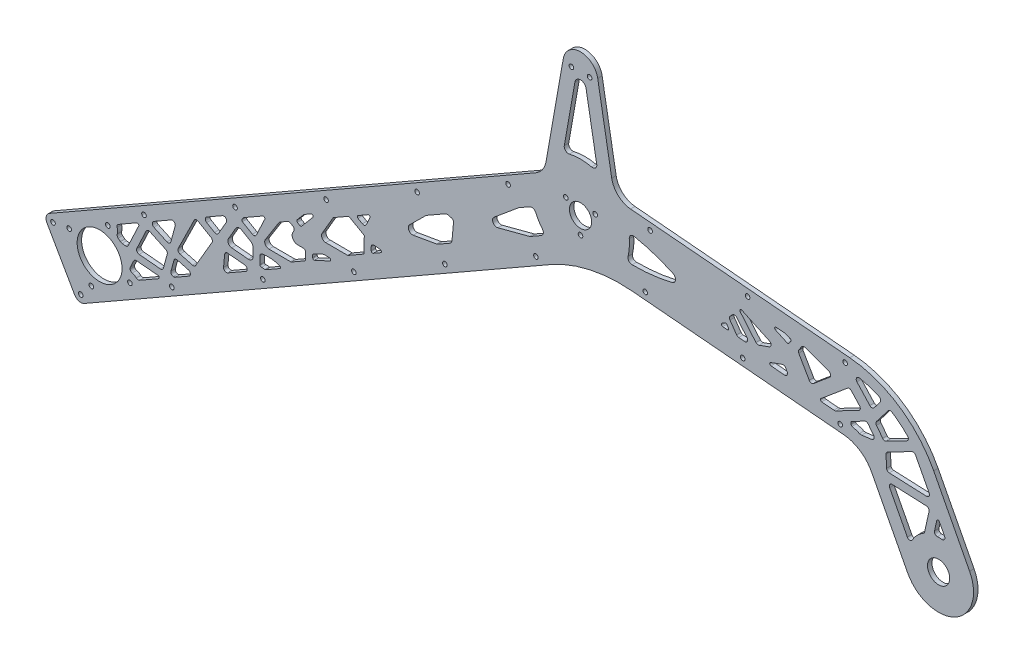
SolidWorks part; units mm, degrees
material "6061-T6 (SS)"
ref_plane "Front Plane" through (0, 0, 0) normal (0, 0, 1) x (1, 0, 0)
ref_plane "Top Plane" through (0, 0, 0) normal (0, 1, 0) x (1, 0, 0)
ref_plane "Right Plane" through (0, 0, 0) normal (1, 0, 0) x (0, 0, -1)
sketch "Reference Sketch" plane through (0, 0, 0) normal (0, 0, 1) x (1, 0, 0)
  line L0 (-343.92, -196.825) -> (0, 0) construction
  line L1 (-243.92, 103.175) -> (356.08, 103.175) construction
  line L2 (-243.92, 103.175) -> (-243.92, 0) construction
  line L3 (-243.92, 0) -> (356.08, 0) construction
  line L4 (356.08, 103.175) -> (356.08, 0) construction
  line L5 (0, 0) -> (256.08, -92.7116) construction
  line L6 (256.08, -92.7116) -> (56.08, -196.825) construction
  line L7 (256.08, -92.7116) -> (456.08, -196.825) construction
  line L8 (-343.92, -196.825) -> (56.08, -196.825) construction
  line L9 (56.08, -196.825) -> (456.08, -196.825) construction
  circle A1 centre (-343.92, -196.825) radius 100 construction
  circle A2 centre (56.08, -196.825) radius 100 construction
  circle A3 centre (456.08, -196.825) radius 100 construction
  circle A4 centre (-343.92, -196.825) radius 16.05 construction
  circle A5 centre (-343.92, -196.825) radius 28.55 construction
  circle A6 centre (-343.92, -196.825) radius 38.55 construction
  circle A7 centre (-343.92, -196.825) radius 33.55 construction
  point P13 (-343.92, -296.825)
  point P14 (556.08, -196.825)
  point P17 (-443.92, -196.825)
  dimension "D3" = 32.1
  dimension "D5" = 200
  dimension "D9" = 57.1
  dimension "D10" = 10
  dimension "D11" = 5
  dimension "D1" = 600
  dimension "D2" = 103.175
  dimension "D4" = 243.92
  dimension "D6" = 125
  dimension "D7" = 400
  dimension "D8" = 1000
sketch "Sketch2" plane through (0, 0, 0) normal (0, 0, 1) x (1, 0, 0)
  line L0 (-379.7168, -188.5069) -> (-32.0065, 10.4873)
  line L1 (-354.8814, -231.9028) -> (-21.5627, -41.1449)
  line L2 (-343.92, -196.825) -> (0, 0) construction
  line L3 (-184.3777, -76.7146) -> (-159.5423, -120.1104) construction
  line L4 (-24.685, 20.9013) -> (-12.3101, 91.0831)
  line L5 (12.3101, 91.0831) -> (22.322, 34.3028)
  line L6 (0, 98.4125) -> (0, 112.7) construction
  line L7 (-5.4848, 79.4125) -> (5.4848, 79.4125) construction
  line L8 (5.4848, 79.4125) -> (10.9697, 88.9125) construction
  line L9 (10.9697, 88.9125) -> (5.4848, 98.4125) construction
  line L10 (5.4848, 98.4125) -> (-5.4848, 98.4125) construction
  line L11 (-5.4848, 98.4125) -> (-10.9697, 88.9125) construction
  line L12 (-10.9697, 88.9125) -> (-5.4848, 79.4125) construction
  line L13 (-243.92, 103.175) -> (356.08, 103.175) construction
  line L14 (0, 88.9125) -> (0, 0) construction
  line L15 (35.7868, 21.9646) -> (192.5861, 8.2464)
  line L16 (252.5753, -31.8371) -> (278.2553, -81.1679)
  line L17 (233.9047, -104.2553) -> (208.2247, -54.9245)
  line L18 (36.8237, -28.3172) -> (188.2284, -41.5633)
  line L19 (0, 0) -> (192.5861, -16.8491) construction
  line L21 (-365.6311, -190.9191) -> (-338.0141, -175.1139) construction
  line L22 (-381.5729, -195.33) -> (-361.7045, -230.0467)
  line L23 (256.08, -92.7116) -> (56.08, -196.825) construction
  line L25 (-243.92, 0) -> (356.08, 0) construction
  circle A0 centre (0, 0) radius 7.9375
  circle A1 centre (-343.92, -196.825) radius 16.05
  arc A3 (-12.3101, 91.0831) -> (12.3101, 91.0831) centre (0, 88.9125) cw
  circle A4 centre (0, 88.9125) radius 6.5 construction
  circle A5 centre (-6.5, 88.9125) radius 1.65
  circle A6 centre (6.5, 88.9125) radius 1.65
  circle A7 centre (0, 88.9125) radius 9.5 construction
  arc A8 (252.5753, -31.8371) -> (192.5861, 8.2464) centre (186.0495, -66.4682) ccw
  circle A9 centre (256.08, -92.7116) radius 7.9375
  arc A10 (278.2553, -81.1679) -> (233.9047, -104.2553) centre (256.08, -92.7116) cw
  arc A11 (-21.5627, -41.1449) -> (36.8237, -28.3172) centre (28.1082, -127.9366) cw
  arc A12 (188.2284, -41.5633) -> (208.2247, -54.9245) centre (186.0495, -66.4682) cw
  arc A13 (22.322, 34.3028) -> (35.7868, 21.9646) centre (37.0941, 36.9075) ccw
  arc A14 (-32.0065, 10.4873) -> (-24.685, 20.9013) centre (-39.4572, 23.506) ccw
  circle A17 centre (-343.92, -196.825) radius 22.5 construction
  circle A18 centre (-365.6311, -190.9191) radius 1.65
  circle A19 centre (-338.0141, -175.1139) radius 1.65
  circle A20 centre (-322.2089, -202.7309) radius 1.65
  circle A21 centre (-349.8259, -218.5361) radius 1.65
  arc A27 (-379.7168, -188.5069) -> (-381.5729, -195.33) centre (-377.2333, -192.8465) ccw
  arc A28 (-361.7045, -230.0467) -> (-354.8814, -231.9028) centre (-357.3649, -227.5632) ccw
  circle A29 centre (-343.92, -196.825) radius 33.55 construction
  circle A32 centre (-343.92, -196.825) radius 38.55 construction
  point P16 (-171.96, -98.4125)
  point P64 (-343.92, -196.825)
  dimension "D1" = 15.875
  dimension "D2" = 32.1
  dimension "D3" = 45
  dimension "D5" = 13
  dimension "D6" = 3.3
  dimension "D7" = 6
  dimension "D12" = 50
  dimension "D14" = 100
  dimension "D16" = 15
  dimension "D17" = 5
  dimension "D18" = 25
  dimension "D19" = 3.3
  dimension "D15" = 4
  dimension "D4" = 50
  dimension "D8" = 19
  dimension "D9" = 14.2875
  dimension "D10" = 9.525
  dimension "D11" = 10
  dimension "D13" = 50
extrude "Base" add sketch "Sketch2" along normal blind 3.175
sketch "Sketch3" plane through (0, 0, 3.175) normal (0, 0, 1) x (1, 0, 0)
  line L0 (-343.92, -196.825) -> (0, 0) construction
  line L5 (0, 0) -> (197.3986, -17.2701) construction
  line L6 (192.5861, 8.2464) -> (35.7868, 21.9646) construction
  line L9 (36.8237, -28.3172) -> (188.2284, -41.5633) construction
  line L10 (-31.8958, -41.2976) -> (0, 0) construction
  line L11 (0, 0) -> (46.2693, -24.1244) construction
  circle A0 centre (-357.3649, -227.5632) radius 1.65
  circle A1 centre (-343.92, -196.825) radius 33.55 construction
  arc A2 (-361.7045, -230.0467) -> (-354.8814, -231.9028) centre (-357.3649, -227.5632) ccw construction
  circle A3 centre (-292.2711, -190.3101) radius 1.65
  circle A4 centre (-227.1773, -153.057) radius 1.65
  circle A5 centre (-162.0835, -115.8038) radius 1.65
  circle A6 centre (-96.9897, -78.5507) radius 1.65
  circle A7 centre (-31.8958, -41.2976) radius 1.65
  circle A8 centre (-312.1394, -155.5934) radius 1.65
  circle A9 centre (-377.2333, -192.8465) radius 1.65
  circle A10 centre (-247.0456, -118.3403) radius 1.65
  circle A11 centre (-181.9518, -81.0871) radius 1.65
  circle A12 centre (-116.858, -43.834) radius 1.65
  circle A13 centre (-51.7642, -6.5809) radius 1.65
  circle A14 centre (46.2693, -24.1244) radius 1.65
  circle A15 centre (116.0029, -30.2253) radius 1.65
  circle A16 centre (185.7366, -36.3262) radius 1.65
  circle A17 centre (189.2228, 3.5215) radius 1.65
  circle A18 centre (119.4892, 9.6224) radius 1.65
  circle A19 centre (49.7555, 15.7234) radius 1.65
  dimension "D1" = 3.3
  dimension "D2" = 6
  dimension "D3" = 5
  dimension "D5" = 3
  dimension "D4" = 75
  dimension "D6" = 70
extrude "Strut Holes" cut sketch "Sketch3" against normal through all
sketch "Sketch6" plane through (0, 0, 3.175) normal (0, 0, 1) x (1, 0, 0)
  line L0 (-315.2692, -197.7109) -> (-301.7593, -189.9792)
  line L1 (-354.8814, -231.9028) -> (-21.5627, -41.1449) construction
  line L2 (-289.845, -183.1607) -> (-279.9388, -177.4914)
  line L3 (-225.0683, -146.089) -> (-215.0659, -140.3647)
  line L4 (-202.4189, -105.5114) -> (-200.6862, -106.5205)
  line L5 (-330.4255, -170.6672) -> (-317.3783, -163.2003)
  line L6 (-32.0065, 10.4873) -> (-379.7168, -188.5069) construction
  line L7 (-315.9769, -164.4942) -> (-323.4022, -180.2613)
  line L8 (-325.3934, -181.4009) -> (-327.8261, -181.1787)
  line L9 (-302.165, -188.1154) -> (-317.5291, -186.7124)
  line L10 (-319.5204, -187.852) -> (-321.9207, -192.9489)
  line L11 (-295.5333, -171.6316) -> (-298.2962, -181.7883)
  line L12 (-300.4079, -183.2551) -> (-315.6625, -181.8621)
  line L13 (-317.2901, -179.0183) -> (-310.6415, -164.9005)
  line L14 (-307.9799, -163.9432) -> (-296.6111, -169.2972)
  line L15 (-280.4073, -173.8257) -> (-288.2923, -171.6808)
  line L16 (-290.7472, -173.0857) -> (-292.8686, -180.8843)
  line L17 (-292.7787, -149.122) -> (-305.2156, -156.2396)
  line L18 (-305.0743, -159.7848) -> (-295.766, -164.1685)
  line L19 (-292.984, -162.8841) -> (-289.8554, -151.3828)
  line L20 (-286.4122, -167.0105) -> (-277.4777, -169.4409)
  line L21 (-275.2245, -168.5176) -> (-263.487, -148.3649)
  line L22 (-264.2087, -145.6301) -> (-273.4911, -140.2238)
  line L23 (-276.2919, -141.0684) -> (-287.6814, -164.1971)
  line L24 (-267.3269, -134.556) -> (-255.9817, -128.0631)
  line L25 (-253.26, -130.8055) -> (-258.9575, -140.5878)
  line L26 (-261.6923, -141.3094) -> (-267.3401, -138.02)
  line L27 (-255.2613, -159.7424) -> (-254.4886, -151.2802)
  line L28 (-252.315, -149.4703) -> (-240.2297, -150.5739)
  line L29 (-292.2711, -190.3101) -> (-299.0066, -188.4038) construction
  line L30 (-252.2762, -161.6601) -> (-239.4181, -154.3014)
  line L31 (-246.5402, -131.1894) -> (-251.7948, -140.2114)
  line L32 (-249.4752, -144.7088) -> (-237.508, -145.8016)
  line L33 (-234.2352, -142.8254) -> (-234.2117, -136.6339)
  line L34 (-235.7018, -134.0302) -> (-242.4379, -130.1069)
  line L35 (-229.2226, -139.4963) -> (-229.2439, -145.1246)
  line L36 (-241.7536, -124.7193) -> (-234.6398, -128.8625)
  line L37 (-231.8238, -127.9864) -> (-225.7969, -115.1887)
  line L38 (-227.1983, -113.8948) -> (-240.4869, -121.4998)
  line L39 (-215.6688, -112.1749) -> (-225.38, -127.5855)
  line L40 (-222.8533, -132.1849) -> (-207.4544, -132.2434)
  line L41 (-206.4534, -131.9792) -> (-197.5057, -126.8584)
  line L42 (-196.4991, -125.1302) -> (-196.4845, -121.2849)
  line L43 (-198.4769, -119.2773) -> (-202.2607, -119.2629)
  line L44 (-205.6297, -113.1304) -> (-205.0269, -112.1739)
  line L45 (-205.7124, -109.3794) -> (-207.4618, -108.3605)
  line L46 (-209.4618, -108.3529) -> (-214.9702, -111.5053)
  line L47 (-223.2993, -137.1832) -> (-189.5978, -137.3112) construction
  line L48 (-199.4194, -106.3021) -> (-191.3609, -96.7721)
  line L49 (-192.6212, -95.2585) -> (-197.479, -98.0386)
  line L50 (-198.0128, -98.4831) -> (-202.6792, -104.0016)
  line L51 (-191.4798, -120.0542) -> (-191.4866, -121.8475)
  line L52 (-190.0674, -122.7592) -> (-179.2455, -117.7628)
  line L54 (-190.899, -119.1501) -> (-184.1308, -116.0253)
  line L55 (-183.2849, -115.8411) -> (-179.6609, -115.8549)
  line L56 (-166.4011, -107.9052) -> (-182.2049, -107.8452)
  line L57 (-184.7858, -103.3353) -> (-176.832, -89.6789)
  line L58 (-176.832, -89.6789) -> (-165.639, -83.2731)
  line L59 (-165.639, -83.2731) -> (-154.6405, -89.6789)
  line L60 (-154.6405, -89.6789) -> (-154.6842, -101.1996)
  line L61 (-154.6842, -101.1996) -> (-166.4011, -107.9052)
  line L62 (-176.832, -89.6789) -> (-166.4011, -107.9052) construction
  line L63 (-149.6667, -96.5998) -> (-149.6576, -94.1811)
  line L64 (-147.4757, -92.197) -> (-143.2847, -92.5797)
  line L65 (-142.8789, -94.4434) -> (-148.17, -97.4715)
  line L66 (-159.1247, -79.5451) -> (-152.014, -75.4756)
  line L67 (-150.6126, -76.7696) -> (-153.1821, -82.2258)
  line L68 (-155.9981, -83.102) -> (-159.1313, -81.2771)
  line L69 (-154.1121, -84.2004) -> (-149.6493, -91.9985) construction
  line L70 (-90.8199, -49.6985) -> (-91.8964, -61.4879)
  line L71 (-93.3939, -63.8188) -> (-101.9943, -68.7409)
  line L72 (-102.9747, -69.0935) -> (-119.6299, -71.9651)
  line L73 (-122.2529, -66.8794) -> (-110.6811, -55.3952)
  line L74 (-110.058, -54.9208) -> (-96.7247, -47.2901)
  line L75 (-94.4471, -46.9991) -> (-92.2866, -47.5868)
  line L76 (-102.4534, -69.0036) -> (-110.4008, -55.117) construction
  line L78 (-28.0968, -26.4494) -> (-35.8254, -30.8725)
  line L79 (-36.5501, -31.1694) -> (-59.134, -37.129)
  line L80 (-61.819, -31.9228) -> (-44.3172, -17.3499)
  line L81 (-43.8877, -17.0516) -> (-36.2746, -12.6946)
  line L82 (-44.1155, -17.182) -> (-36.1682, -31.0687) construction
  line L83 (-11.5997, 37.5245) -> (-3.9861, 80.7029)
  line L84 (3.9861, 80.7029) -> (11.5997, 37.5245)
  line L85 (22.322, 34.3028) -> (12.3101, 91.0831) construction
  line L86 (-12.3101, 91.0831) -> (-24.685, 20.9013) construction
  line L87 (192.5861, 8.2464) -> (35.7868, 21.9646) construction
  line L88 (36.8237, -28.3172) -> (188.2284, -41.5633) construction
  line L89 (-227.1773, -153.057) -> (-233.9128, -151.1507) construction
  line L90 (246.076, -72.9136) -> (249.254, -58.5784)
  line L91 (247.3887, -56.1475) -> (222.9622, -55.081)
  line L92 (221.1009, -58.0026) -> (233.7353, -82.273)
  line L93 (208.2247, -54.9245) -> (233.9047, -104.2553) construction
  line L94 (253.1337, -68.7997) -> (254.752, -61.5)
  line L95 (256.6153, -61.2547) -> (260.3456, -68.4206)
  line L96 (278.2553, -81.1679) -> (252.5753, -31.8371) construction
  line L97 (249.3108, -47.2228) -> (239.5975, -28.5637)
  line L98 (236.9, -27.7132) -> (219.5656, -36.7369)
  line L99 (218.491, -38.5982) -> (218.8608, -47.0688)
  line L100 (220.7717, -48.9796) -> (247.4495, -50.1444)
  line L101 (233.4135, -22.7639) -> (218.6181, -30.4658)
  line L102 (216.1079, -29.9093) -> (211.6718, -24.1281)
  line L103 (211.6718, -21.693) -> (220.0072, -10.8302)
  line L104 (209.6166, -31.3057) -> (205.7463, -26.2618)
  line L105 (203.2361, -25.7053) -> (194.0101, -30.5081)
  line L106 (193.4718, -31.3951) -> (193.4718, -32.4967)
  line L107 (201.069, -35.4569) -> (208.2909, -34.5061)
  line L108 (214.3031, -8.4078) -> (209.9577, -14.0708)
  line L109 (197.6887, -4.156) -> (206.8964, -14.2045)
  line L110 (193.6814, -11.6243) -> (199.5455, -18.0239)
  line L111 (198.9945, -21.1491) -> (182.8075, -29.5754)
  line L112 (181.1608, -29.903) -> (172.4826, -29.1438)
  line L113 (171.927, -27.3815) -> (190.9213, -11.4434)
  line L114 (178.1992, -11.0225) -> (166.5918, -20.7623)
  line L115 (163.5742, -20.2302) -> (156.048, -7.1944)
  line L116 (156.1417, -5.0472) -> (158.1885, -2.1242)
  line L117 (160.5108, -1.3919) -> (177.5977, -7.611)
  line L118 (146.6448, -20.9077) -> (147.747, -22.8167)
  line L119 (145.8406, -25.8091) -> (136.23, -24.9682)
  line L120 (135.9751, -23.0324) -> (144.2287, -20.0283)
  line L121 (134.9743, -13.819) -> (127.6718, -16.4769)
  line L122 (125.4557, -15.8831) -> (114.1985, -2.4673)
  line L123 (115.3872, -0.9182) -> (135.1355, -10.127)
  line L124 (139.4306, -1.096) -> (147.8318, -5.0136)
  line L125 (149.0736, -4.6809) -> (150.4259, -2.7496)
  line L126 (149.9488, -1.2363) -> (146.0985, 0.1651)
  line L127 (145.3339, 0.3346) -> (139.9404, 0.8065)
  line L128 (111.6605, -7.2212) -> (119.0455, -16.0223)
  line L129 (117.3391, -19.3002) -> (113.1162, -18.9308)
  line L130 (111.6522, -18.0855) -> (106.8775, -11.2665)
  line L131 (107.1016, -8.7052) -> (108.7142, -7.0926)
  line L132 (104.7039, -15.1361) -> (105.7554, -16.6377)
  line L133 (104.8491, -18.2075) -> (101.6773, -17.93)
  line L134 (101.2644, -16.0678) -> (103.3847, -14.8436)
  arc A0 (-317.584, -197.4764) -> (-320.5599, -195.9279) centre (-322.2089, -202.7309) ccw
  arc A1 (-291.1568, -183.3993) -> (-291.2348, -183.3872) centre (-292.2711, -190.3101) ccw
  arc A2 (-225.7665, -146.2006) -> (-228.1106, -146.1195) centre (-227.1773, -153.057) ccw
  arc A4 (-322.0747, -194.2209) -> (-322.0953, -194.053) centre (-343.92, -196.825) ccw
  arc A5 (-331.3132, -177.1382) -> (-331.3392, -173.0054) centre (-338.0141, -175.1139) ccw
  arc A6 (-329.0005, -180.6569) -> (-330.6088, -179.309) centre (-343.92, -196.825) ccw
  arc A8 (-227.5555, -137.5318) -> (-215.2363, -138.5515) centre (-223.3943, -162.1831) cw
  arc A9 (-241.9747, -123.1658) -> (-241.1717, -122.1478) centre (-247.0456, -118.3403) ccw
  arc A10 (-32.0383, -14.0906) -> (-27.2511, -21.9631) centre (0, 0) ccw
  arc A11 (-251.7948, -140.2114) -> (-249.4752, -144.7088) centre (-249.2024, -141.7213) ccw
  arc A12 (-225.38, -127.5855) -> (-222.8533, -132.1849) centre (-222.8419, -129.1849) ccw
  arc A13 (-182.2049, -107.8452) -> (-184.7858, -103.3353) centre (-182.1935, -104.8452) cw
  arc A14 (-119.6299, -71.9651) -> (-122.2529, -66.8794) centre (-120.1396, -69.0087) cw
  arc A15 (-59.134, -37.129) -> (-61.819, -31.9228) centre (-59.8994, -34.2283) cw
  arc A16 (-7.9627, 34.0822) -> (7.9627, 34.0822) centre (0, 0) cw
  arc A17 (-3.9861, 80.7029) -> (3.9861, 80.7029) centre (0, 80) cw
  arc A18 (34.8636, 3.0867) -> (34.0029, -8.2948) centre (0, 0) cw
  arc A19 (38.4335, 6.2944) -> (66.0977, -2.7713) centre (15.1723, -111.4295) cw
  arc A20 (66.0977, -2.7713) -> (65.4856, -8.7407) centre (64.749, -5.6491) cw
  arc A21 (36.898, -12.0057) -> (65.4856, -8.7407) centre (37.6733, 107.9918) ccw
  arc A22 (245.141, -74.2025) -> (237.26, -82.3165) centre (256.08, -92.7116) ccw
  arc A23 (258.3595, -71.3328) -> (255.1708, -71.2308) centre (256.08, -92.7116) ccw
  arc A24 (222.6875, -10.3732) -> (233.9189, -19.5905) centre (186.0495, -66.4682) cw
  arc A25 (252.5753, -31.8371) -> (192.5861, 8.2464) centre (186.0495, -66.4682) ccw construction
  arc A26 (194.2312, -33.4673) -> (199.4914, -35.2382) centre (186.0495, -66.4682) cw
  arc A27 (208.2247, -54.9245) -> (188.2284, -41.5633) centre (186.0495, -66.4682) ccw construction
  arc A28 (213.5369, -5.3663) -> (199.5667, -0.8459) centre (186.0495, -66.4682) ccw
  arc A29 (218.8608, -47.0688) -> (220.7717, -48.9796) centre (220.8589, -46.9815) ccw
  arc A30 (239.5975, -28.5637) -> (236.9, -27.7132) centre (237.8235, -29.4872) ccw
  arc A31 (219.5656, -36.7369) -> (218.491, -38.5982) centre (220.4891, -38.5109) ccw
  arc A32 (127.6718, -16.4769) -> (125.4557, -15.8831) centre (126.9878, -14.5975) cw
  arc A33 (-240.4869, -121.4998) -> (-241.1717, -122.1478) centre (-239.4934, -123.2356) ccw
  arc A34 (-234.6398, -128.8625) -> (-231.8238, -127.9864) centre (-233.6332, -127.1343) ccw
  arc A35 (-229.2226, -139.4963) -> (-227.5555, -137.5318) centre (-227.2226, -139.5039) cw
  arc A36 (-315.2692, -197.7109) -> (-317.584, -197.4764) centre (-316.2626, -195.9751) cw
  arc A37 (-322.0747, -194.2209) -> (-320.5599, -195.9279) centre (-320.0887, -193.9842) ccw
  arc A38 (-321.9207, -192.9489) -> (-322.0953, -194.053) centre (-320.1113, -193.801) ccw
  arc A39 (-317.5291, -186.7124) -> (-319.5204, -187.852) centre (-317.711, -188.7042) ccw
  arc A40 (-323.4022, -180.2613) -> (-325.3934, -181.4009) centre (-325.2116, -179.4092) cw
  arc A41 (-327.8261, -181.1787) -> (-329.0005, -180.6569) centre (-327.6442, -179.187) cw
  arc A42 (-331.3132, -177.1382) -> (-330.6088, -179.309) centre (-329.3986, -177.7166) ccw
  arc A43 (-330.4255, -170.6672) -> (-331.3392, -173.0054) centre (-329.4321, -172.403) ccw
  arc A44 (-315.6625, -181.8621) -> (-317.2901, -179.0183) centre (-315.4807, -179.8704) cw
  arc A45 (-298.2962, -181.7883) -> (-300.4079, -183.2551) centre (-300.226, -181.2634) cw
  arc A46 (-289.845, -183.1607) -> (-291.1568, -183.3993) centre (-290.8384, -181.4248) cw
  arc A47 (-292.8686, -180.8843) -> (-291.2348, -183.3872) centre (-290.9387, -181.4092) ccw
  arc A48 (-280.4073, -173.8257) -> (-279.9388, -177.4914) centre (-280.9322, -175.7556) cw
  arc A49 (-288.2923, -171.6808) -> (-290.7472, -173.0857) centre (-288.8173, -173.6107) ccw
  arc A50 (-295.5333, -171.6316) -> (-296.6111, -169.2972) centre (-297.4632, -171.1066) ccw
  arc A51 (-310.6415, -164.9005) -> (-307.9799, -163.9432) centre (-308.8321, -165.7526) cw
  arc A52 (-305.2156, -156.2396) -> (-305.0743, -159.7848) centre (-304.2222, -157.9754) ccw
  arc A53 (-292.7787, -149.122) -> (-289.8554, -151.3828) centre (-291.7853, -150.8578) cw
  arc A54 (-295.766, -164.1685) -> (-292.984, -162.8841) centre (-294.9139, -162.3591) ccw
  arc A55 (-286.4122, -167.0105) -> (-287.6814, -164.1971) centre (-285.8872, -165.0807) cw
  arc A56 (-277.4777, -169.4409) -> (-275.2245, -168.5176) centre (-276.9527, -167.511) ccw
  arc A57 (-263.487, -148.3649) -> (-264.2087, -145.6301) centre (-265.2153, -147.3583) ccw
  arc A58 (-273.4911, -140.2238) -> (-276.2919, -141.0684) centre (-274.4977, -141.952) ccw
  arc A59 (-267.3269, -134.556) -> (-267.3401, -138.02) centre (-266.3335, -136.2918) ccw
  arc A60 (-258.9575, -140.5878) -> (-261.6923, -141.3094) centre (-260.6857, -139.5812) cw
  arc A61 (-254.4886, -151.2802) -> (-252.315, -149.4703) centre (-252.4969, -151.462) cw
  arc A62 (-255.2613, -159.7424) -> (-252.2762, -161.6601) centre (-253.2696, -159.9243) ccw
  arc A63 (-239.4181, -154.3014) -> (-240.2297, -150.5739) centre (-240.4115, -152.5656) ccw
  arc A64 (-255.9817, -128.0631) -> (-253.26, -130.8055) centre (-254.9883, -129.7989) cw
  arc A65 (-207.4544, -132.2434) -> (-206.4534, -131.9792) centre (-207.4468, -130.2434) ccw
  arc A66 (-214.9702, -111.5053) -> (-215.6688, -112.1749) centre (-213.9767, -113.2412) ccw
  arc A67 (-207.4618, -108.3605) -> (-209.4618, -108.3529) centre (-208.4684, -110.0887) ccw
  arc A68 (-205.0269, -112.1739) -> (-205.7124, -109.3794) centre (-206.719, -111.1076) ccw
  arc A69 (-202.2607, -119.2629) -> (-205.6297, -113.1304) centre (-202.2456, -115.263) cw
  arc A70 (-196.4845, -121.2849) -> (-198.4769, -119.2773) centre (-198.4845, -121.2773) ccw
  arc A71 (-197.5057, -126.8584) -> (-196.4991, -125.1302) centre (-198.4991, -125.1226) ccw
  arc A72 (-184.1308, -116.0253) -> (-183.2849, -115.8411) centre (-183.2925, -117.8411) cw
  arc A73 (-197.479, -98.0386) -> (-198.0128, -98.4831) centre (-196.4856, -99.7744) ccw
  arc A74 (-149.6576, -94.1811) -> (-147.4757, -92.197) centre (-147.6576, -94.1887) cw
  arc A75 (-153.1821, -82.2258) -> (-155.9981, -83.102) centre (-154.9915, -81.3737) cw
  arc A76 (-90.8199, -49.6985) -> (-92.2866, -47.5868) centre (-92.8116, -49.5167) ccw
  arc A77 (111.6605, -7.2212) -> (108.7142, -7.0926) centre (110.1284, -8.5068) ccw
  arc A78 (106.8775, -11.2665) -> (107.1016, -8.7052) centre (108.5158, -10.1194) cw
  arc A79 (113.1162, -18.9308) -> (111.6522, -18.0855) centre (113.2905, -16.9384) cw
  arc A80 (119.0455, -16.0223) -> (117.3391, -19.3002) centre (117.5134, -17.3078) cw
  arc A81 (134.9743, -13.819) -> (135.1355, -10.127) centre (134.2903, -11.9396) ccw
  arc A82 (146.6448, -20.9077) -> (144.2287, -20.0283) centre (144.9128, -21.9077) ccw
  arc A83 (147.747, -22.8167) -> (145.8406, -25.8091) centre (146.0149, -23.8167) cw
  arc A84 (156.048, -7.1944) -> (156.1417, -5.0472) centre (157.78, -6.1944) cw
  arc A85 (158.1885, -2.1242) -> (160.5108, -1.3919) centre (159.8268, -3.2713) cw
  arc A86 (178.1992, -11.0225) -> (177.5977, -7.611) centre (176.9136, -9.4904) ccw
  arc A87 (166.5918, -20.7623) -> (163.5742, -20.2302) centre (165.3062, -19.2302) cw
  arc A88 (193.6814, -11.6243) -> (190.9213, -11.4434) centre (192.2068, -12.9755) ccw
  arc A89 (199.5455, -18.0239) -> (198.9945, -21.1491) centre (198.071, -19.375) cw
  arc A90 (209.9577, -14.0708) -> (206.8964, -14.2045) centre (208.371, -12.8533) cw
  arc A91 (213.5369, -5.3663) -> (214.3031, -8.4078) centre (212.7164, -7.1903) cw
  arc A92 (233.9189, -19.5905) -> (233.4135, -22.7639) centre (232.49, -20.9899) cw
  arc A93 (222.6875, -10.3732) -> (220.0072, -10.8302) centre (221.5939, -12.0477) ccw
  arc A94 (211.6718, -24.1281) -> (211.6718, -21.693) centre (213.2585, -22.9105) cw
  arc A95 (218.6181, -30.4658) -> (216.1079, -29.9093) centre (217.6946, -28.6918) cw
  arc A96 (205.7463, -26.2618) -> (203.2361, -25.7053) centre (204.1595, -27.4793) ccw
  arc A97 (209.6166, -31.3057) -> (208.2909, -34.5061) centre (208.0299, -32.5232) cw
  arc A98 (246.076, -72.9136) -> (245.141, -74.2025) centre (244.1234, -72.4807) cw
  arc A99 (249.254, -58.5784) -> (247.3887, -56.1475) centre (247.3014, -58.1456) ccw
  arc A100 (222.9622, -55.081) -> (221.1009, -58.0026) centre (222.8749, -57.0791) ccw
  arc A101 (233.7353, -82.273) -> (237.26, -82.3165) centre (235.5093, -81.3495) ccw
  arc A102 (260.3456, -68.4206) -> (258.3595, -71.3328) centre (258.5716, -69.344) cw
  arc A103 (253.1337, -68.7997) -> (255.1708, -71.2308) centre (255.0863, -69.2326) ccw
  arc A104 (249.3108, -47.2228) -> (247.4495, -50.1444) centre (247.5367, -48.1463) cw
  arc A105 (199.5667, -0.8459) -> (197.6887, -4.156) centre (199.1632, -2.8048) ccw
  arc A106 (-215.2363, -138.5515) -> (-215.0659, -140.3647) centre (-215.5626, -139.4968) cw
  arc A107 (-301.7593, -189.9792) -> (-302.165, -188.1154) centre (-302.256, -189.1113) ccw
  arc A108 (-317.3783, -163.2003) -> (-315.9769, -164.4942) centre (-316.8815, -164.0682) cw
  arc A109 (-225.7969, -115.1887) -> (-227.1983, -113.8948) centre (-226.7016, -114.7627) ccw
  arc A110 (-241.7536, -124.7193) -> (-241.9747, -123.1658) centre (-241.2503, -123.8551) cw
  arc A111 (-225.7665, -146.2006) -> (-225.0683, -146.089) centre (-225.565, -145.2211) ccw
  arc A112 (-229.2439, -145.1246) -> (-228.1106, -146.1195) centre (-228.2439, -145.1284) ccw
  arc A113 (-202.4189, -105.5114) -> (-202.6792, -104.0016) centre (-201.9156, -104.6473) cw
  arc A114 (-200.6862, -106.5205) -> (-199.4194, -106.3021) centre (-200.183, -105.6564) ccw
  arc A115 (-191.4798, -120.0542) -> (-190.899, -119.1501) centre (-190.4798, -120.058) cw
  arc A116 (-191.4866, -121.8475) -> (-190.0674, -122.7592) centre (-190.4866, -121.8513) ccw
  arc A117 (-191.3609, -96.7721) -> (-192.6212, -95.2585) centre (-192.1245, -96.1264) ccw
  arc A118 (-179.2455, -117.7628) -> (-179.6609, -115.8549) centre (-179.6647, -116.8549) ccw
  arc A119 (-152.014, -75.4756) -> (-150.6126, -76.7696) centre (-151.5173, -76.3435) cw
  arc A120 (-159.1247, -79.5451) -> (-159.1313, -81.2771) centre (-158.628, -80.413) ccw
  arc A121 (-149.6667, -96.5998) -> (-148.17, -97.4715) centre (-148.6667, -96.6036) ccw
  arc A122 (-143.2847, -92.5797) -> (-142.8789, -94.4434) centre (-143.3756, -93.5755) cw
  arc A123 (101.6773, -17.93) -> (101.2644, -16.0678) centre (101.7644, -16.9338) cw
  arc A124 (104.7039, -15.1361) -> (103.3847, -14.8436) centre (103.8847, -15.7096) ccw
  arc A125 (105.7554, -16.6377) -> (104.8491, -18.2075) centre (104.9362, -17.2113) cw
  arc A126 (114.1985, -2.4673) -> (115.3872, -0.9182) centre (114.9646, -1.8245) cw
  arc A127 (136.23, -24.9682) -> (135.9751, -23.0324) centre (136.3171, -23.972) cw
  arc A128 (139.4306, -1.096) -> (139.9404, 0.8065) centre (139.8532, -0.1897) cw
  arc A129 (172.4826, -29.1438) -> (171.927, -27.3815) centre (172.5698, -28.1476) cw
  arc A130 (194.0101, -30.5081) -> (193.4718, -31.3951) centre (194.4718, -31.3951) ccw
  arc A131 (193.4718, -32.4967) -> (194.2312, -33.4673) centre (194.4718, -32.4967) ccw
  arc A132 (254.752, -61.5) -> (256.6153, -61.2547) centre (255.7283, -61.7164) cw
  arc A133 (146.0985, 0.1651) -> (145.3339, 0.3346) centre (145.0724, -2.654) ccw
  arc A134 (199.4914, -35.2382) -> (201.069, -35.4569) centre (200.6774, -32.4826) ccw
  arc A135 (182.8075, -29.5754) -> (181.1608, -29.903) centre (181.4223, -26.9144) cw
  arc A136 (-7.9627, 34.0822) -> (-11.5997, 37.5245) centre (-8.6452, 37.0035) cw
  arc A137 (7.9627, 34.0822) -> (11.5997, 37.5245) centre (8.6452, 37.0035) ccw
  arc A138 (34.8636, 3.0867) -> (38.4335, 6.2944) centre (37.8519, 3.3513) cw
  arc A139 (34.0029, -8.2948) -> (36.898, -12.0057) centre (36.9174, -9.0058) ccw
  arc A140 (-35.8254, -30.8725) -> (-36.5501, -31.1694) centre (-37.3155, -28.2687) cw
  arc A141 (-44.3172, -17.3499) -> (-43.8877, -17.0516) centre (-42.3976, -19.6554) cw
  arc A142 (-32.0383, -14.0906) -> (-36.2746, -12.6946) centre (-34.7845, -15.2984) ccw
  arc A143 (-27.2511, -21.9631) -> (-28.0968, -26.4494) centre (-29.5869, -23.8456) cw
  arc A144 (-96.7247, -47.2901) -> (-94.4471, -46.9991) centre (-95.2346, -49.8939) cw
  arc A145 (-91.8964, -61.4879) -> (-93.3939, -63.8188) centre (-94.884, -61.2151) cw
  arc A146 (-110.6811, -55.3952) -> (-110.058, -54.9208) centre (-108.5679, -57.5245) cw
  arc A147 (-101.9943, -68.7409) -> (-102.9747, -69.0935) centre (-103.4845, -66.1371) cw
  arc A148 (-246.5402, -131.1894) -> (-242.4379, -130.1069) centre (-243.9478, -132.6992) cw
  arc A149 (-234.2117, -136.6339) -> (-235.7018, -134.0302) centre (-237.2117, -136.6225) ccw
  arc A150 (-237.508, -145.8016) -> (-234.2352, -142.8254) centre (-237.2352, -142.8141) ccw
  arc A151 (150.4259, -2.7496) -> (149.9488, -1.2363) centre (149.6067, -2.176) ccw
  arc A152 (147.8318, -5.0136) -> (149.0736, -4.6809) centre (148.2544, -4.1073) ccw
  point P98 (-116.858, -43.834)
  point P110 (-254.1648, -144.2806)
  point P113 (-228.2654, -132.1643)
  point P143 (34.9003, -2.6394)
  point P203 (218.9408, -48.8997)
  point P206 (238.674, -26.7897)
  point P211 (126.3559, -16.9559)
  point P214 (-240.9361, -121.7569)
  point P217 (-232.7537, -129.961)
  point P220 (-229.2164, -137.8704)
  point P229 (-318.9237, -186.5851)
  point P232 (-323.9988, -181.5282)
  point P235 (-328.5183, -181.1155)
  point P240 (-331.9839, -171.5591)
  point P247 (-290.5028, -183.5371)
  point P252 (-275.7482, -175.0931)
  point P255 (-290.2222, -171.1558)
  point P262 (-308.5502, -158.1479)
  point P265 (-288.588, -146.7237)
  point P268 (-293.6097, -165.184)
  point P271 (-288.7533, -166.3737)
  point P278 (-275.3444, -139.1443)
  point P281 (-270.3335, -136.2766)
  point P288 (-255.6107, -163.5684)
  point P294 (-249.5035, -124.3556)
  point P297 (-206.9185, -132.2454)
  point P300 (-215.403, -111.753)
  point P303 (-208.4596, -107.7794)
  point P308 (-209.4769, -119.2355)
  point P311 (-196.4769, -119.2849)
  point P314 (-196.5035, -126.2849)
  point P329 (110.2575, -5.5492)
  point P334 (112.1872, -18.8495)
  point P337 (122.1491, -19.721)
  point P340 (139.5116, -12.1676)
  point P345 (149.6679, -26.1439)
  point P350 (159.0687, -0.8671)
  point P353 (180.8529, -8.7958)
  point P356 (164.7659, -22.2944)
  point P363 (208.5067, -15.9618)
  point P366 (215.8118, -6.4415)
  point P369 (235.7568, -21.544)
  point P374 (210.7376, -22.9105)
  point P377 (217.1296, -31.2407)
  point P380 (204.7246, -24.9304)
  point P383 (211.7254, -34.054)
  point P390 (219.5014, -54.9299)
  point P393 (235.6626, -85.9753)
  point P396 (262.2729, -72.1228)
  point P401 (250.9103, -50.2955)
  point P406 (-213.2581, -139.3301)
  point P412 (-314.6256, -161.6249)
  point P415 (-224.4456, -112.3194)
  point P420 (-225.4089, -146.284)
  point P423 (-229.2487, -146.3704)
  point P426 (-203.4487, -104.9116)
  point P431 (-191.4774, -119.4171)
  point P434 (-191.4925, -123.4171)
  point P437 (-187.699, -92.4415)
  point P440 (-175.1502, -115.872)
  point P447 (-149.6733, -98.3319)
  point P450 (-140.1262, -92.8681)
  point P453 (98.5177, -17.6536)
  point P458 (106.9854, -18.3944)
  point P463 (131.7364, -24.5751)
  point P468 (170.0776, -28.9333)
  point P471 (193.4718, -30.7883)
  point P474 (193.4718, -33.2883)
  point P477 (255.3467, -58.8176)
  point P484 (182.0319, -29.9792)
  point P491 (34.2849, 7.0387)
  point P494 (32.91, -11.9136)
  point P505 (-24.8853, -24.6115)
  point P508 (-95.6462, -46.6729)
  point P511 (-92.0384, -63.0431)
  point P524 (-234.2477, -146.0993)
  point P527 (151.1734, -1.682)
  point P530 (148.5923, -5.3682)
  dimension "D1" = 14
  dimension "D2" = 10
  dimension "D3" = 2
  dimension "D5" = 22
  dimension "D6" = 9
  dimension "D12" = 5
  dimension "D19" = 7
  dimension "D31" = 7
  dimension "D40" = 25
  dimension "D44" = 19
  dimension "D62" = 5
  dimension "D92" = 35
  dimension "D96" = 3
  dimension "D97" = 10
  dimension "D100" = 15
  dimension "D104" = 30
  dimension "D105" = 120
  dimension "D107" = 43
  dimension "D116" = 65
  dimension "D117" = 8
  dimension "D127" = 9
  dimension "D128" = 6
  dimension "D171" = 2
  dimension "D172" = 1
  dimension "D173" = 3
  dimension "D174" = 1
  dimension "D175" = 4
  dimension "D7" = 35
  dimension "D8" = 35
  dimension "D9" = 20
  dimension "D10" = 22
  dimension "D11" = 20
  dimension "D13" = 5
  dimension "D14" = 45
  dimension "D15" = 45
  dimension "D16" = 17
  dimension "D17" = 15
  dimension "D18" = 5
  dimension "D20" = 55
  dimension "D21" = 5
  dimension "D22" = 45
  dimension "D23" = 23
  dimension "D24" = 34
  dimension "D25" = 60
  dimension "D26" = 5
  dimension "D27" = 5
  dimension "D28" = 5
  dimension "D29" = 30
  dimension "D30" = 24
  dimension "D32" = 55
  dimension "D33" = 35
  dimension "D34" = 25
  dimension "D35" = 5
  dimension "D36" = 6
  dimension "D37" = 60
  dimension "D38" = 5
  dimension "D39" = 20
  dimension "D41" = 11
  dimension "D42" = 35
  dimension "D43" = 60
  dimension "D45" = 19.5
  dimension "D46" = 5
  dimension "D47" = 5
  dimension "D48" = 30
  dimension "D49" = 5
  dimension "D50" = 14
  dimension "D51" = 13
  dimension "D52" = 8.5
  dimension "D53" = 60
  dimension "D54" = 12
  dimension "D55" = 7
  dimension "D56" = 22
  dimension "D57" = 28
  dimension "D58" = 60
  dimension "D59" = 15
  dimension "D60" = 8
  dimension "D61" = 13
  dimension "D63" = 12
  dimension "D64" = 20
  dimension "D65" = 5
  dimension "D66" = 65
  dimension "D67" = 25
  dimension "2" = 18
  dimension "D68" = 8
  dimension "D69" = 4
  dimension "D70" = 14
  dimension "D71" = 15
  dimension "D72" = 13.5
  dimension "D73" = 60
  dimension "D74" = 60
  dimension "D75" = 8
  dimension "D76" = 5
  dimension "D77" = 35
  dimension "D78" = 0.5076
  dimension "D79" = 5
  dimension "D80" = 11
  dimension "D81" = 35
  dimension "D82" = 16
  dimension "D83" = 18
  dimension "D84" = 55
  dimension "D85" = 45
  dimension "D86" = 20
  dimension "D87" = 15
  dimension "D88" = 12
  dimension "D89" = 17
  dimension "D90" = 16
  dimension "D91" = 18
  dimension "D93" = 15
  dimension "D94" = 10
  dimension "D95" = 13
  dimension "D98" = 10
  dimension "D99" = 80
  dimension "D101" = 16
  dimension "D102" = 22
  dimension "D103" = 22
  dimension "D106" = 7
  dimension "D108" = 10
  dimension "D109" = 40
  dimension "D110" = 10
  dimension "D111" = 6
  dimension "D112" = 60
  dimension "D113" = 35
  dimension "D114" = 15
  dimension "D115" = 6
  dimension "D118" = 26.5
  dimension "D119" = 6
  dimension "D120" = 85
  dimension "D121" = 85
  dimension "D122" = 32
  dimension "D123" = 21
  dimension "D124" = 80
  dimension "D125" = 75
  dimension "D126" = 6
  dimension "D129" = 10.5
  dimension "D130" = 80
  dimension "D131" = 12
  dimension "D132" = 8
  dimension "D133" = 6
  dimension "D134" = 2.5
  dimension "D135" = 100
  dimension "D136" = 11.5
  dimension "D137" = 60
  dimension "D138" = 11
  dimension "D139" = 45
  dimension "D140" = 12
  dimension "D141" = 8.5
  dimension "D142" = 12
  dimension "D143" = 18
  dimension "D144" = 80
  dimension "D145" = 21
  dimension "D146" = 60
  dimension "D147" = 60
  dimension "D148" = 15
  dimension "D149" = 12
  dimension "D150" = 18
  dimension "D151" = 25
  dimension "D152" = 9
  dimension "D153" = 12
  dimension "D154" = 6
  dimension "D155" = 15
  dimension "D156" = 20
  dimension "D157" = 10
  dimension "D158" = 13.5
  dimension "D159" = 4.5
  dimension "D160" = 45
  dimension "D161" = 14
  dimension "D162" = 5
  dimension "D163" = 10
  dimension "D164" = 16
  dimension "D165" = 50
  dimension "D166" = 18.5
  dimension "D167" = 50
  dimension "D168" = 4
  dimension "D169" = 8.5
  dimension "D170" = 35
extrude "Lightening Holes" cut sketch "Sketch6" against normal through all
sketch "Sketch7" plane through (0, 0, 3.175) normal (0, 0, 1) x (1, 0, 0)
  circle A0 centre (-10.5, 6.0622) radius 1.65
  circle A1 centre (10.5, 6.0622) radius 1.65
  circle A2 centre (0, -12.1244) radius 1.65
  point P3 (0, 0)
  point P4 (0, 0)
  point P8 (0, 0)
  dimension "D1" = 3.3
  dimension "D3" = 21
  dimension "D2" = 3
extrude "Cut-Extrude1" cut sketch "Sketch7" against normal through all
